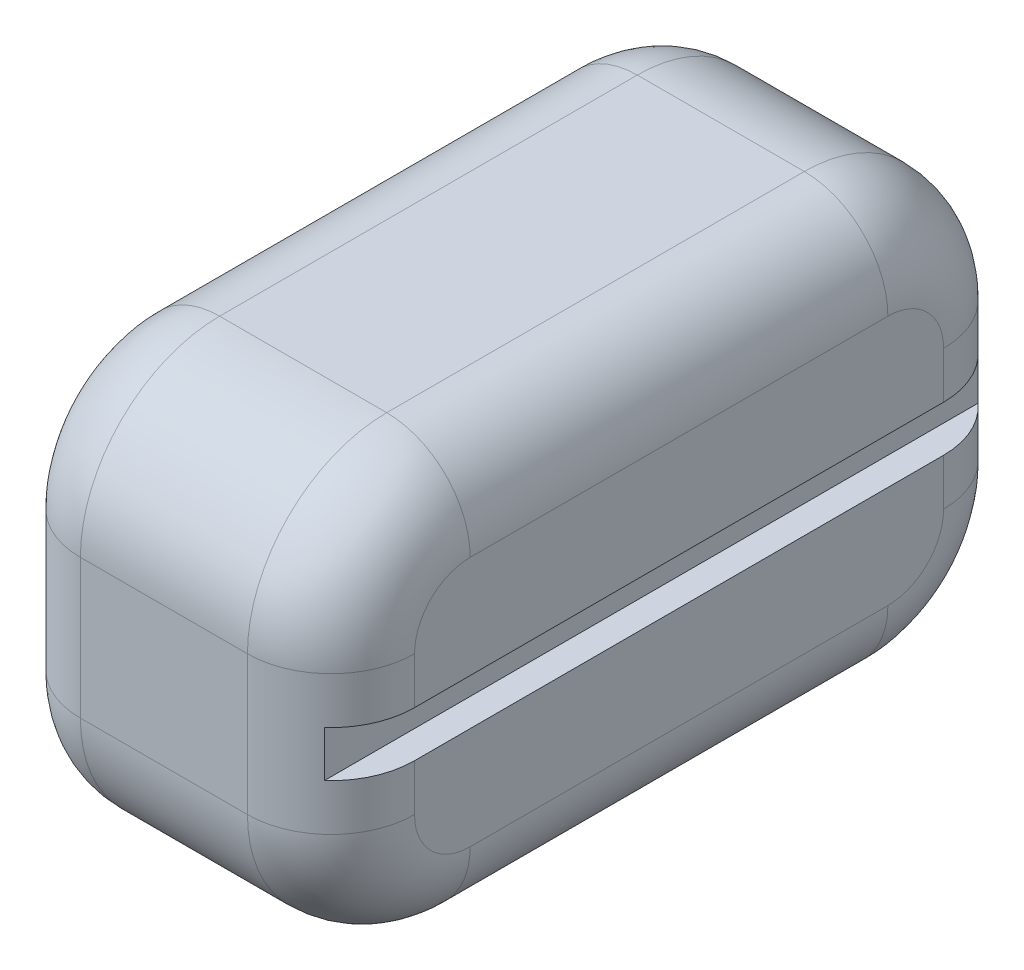
SolidWorks part; units mm, degrees
ref_plane "Front Plane" through (0, 0, 0) normal (0, 0, 1) x (1, 0, 0)
ref_plane "Top Plane" through (0, 0, 0) normal (0, 1, 0) x (1, 0, 0)
ref_plane "Right Plane" through (0, 0, 0) normal (1, 0, 0) x (0, 0, -1)
sketch "Sketch1" plane through (0, 0, 0) normal (1, 0, 0) x (0, 0, -1)
  line L1 (-12.5, -7.5) -> (12.5, -7.5)
  line L2 (-12.5, -7.5) -> (-12.5, 7.5)
  line L3 (-12.5, 7.5) -> (12.5, 7.5)
  line L4 (12.5, -7.5) -> (12.5, 7.5)
  line L5 (0, 7.5) -> (0, -7.5) construction
  line L6 (-12.5, 0) -> (12.5, 0) construction
  point P0 (0, 0)
  dimension "D1" = 15
  dimension "D2" = 25
extrude "Boss-Extrude1" add sketch "Sketch1" along normal blind 12
sketch "Sketch2" plane through (0, 0, 0) normal (0, 1, 0) x (1, 0, 0)
  line L8 (-4, 0) -> (10, 0) construction
  line L9 (0, -10.5) -> (10, -10.5)
  line L10 (10, -10.5) -> (10, 10.5)
  line L11 (10, 10.5) -> (0, 10.5)
  line L12 (-4, -10.5) -> (10, -10.5) construction
  line L13 (10, -10.5) -> (10, 10.5) construction
  line L14 (10, 10.5) -> (-4, 10.5) construction
  line L16 (-4, 12.5) -> (-4, -12.5)
  line L17 (-4, 12.5) -> (-4, -12.5) construction
  circle A3 centre (3, 0) radius 7
  dimension "D1" = 2
  dimension "D2" = 4
extrude "Cut-Extrude1" cut sketch "Sketch2" against normal mid plane 8
ref_plane "Plane1" through (0, -3.8, 0) normal (0, 1, 0) x (1, 0, 0)
sketch "Sketch3" plane through (0, -3.8, 0) normal (0, 1, 0) x (1, 0, 0)
  line L0 (0, -6.3246) -> (0, 6.3246) construction
  line L1 (0, -6.0467) -> (0, 6.0467)
  arc A2 (0.1071, -6.0987) -> (0.1071, 6.0987) centre (3, 0) ccw
  arc A3 (0, -6.0467) -> (0, 6.0467) centre (3, 0) ccw
  dimension "D1" = 0.25
extrude "Boss-Extrude2" add sketch "Sketch3" along normal blind 7.6 separate body
sketch "Sketch4" plane through (0, 0, 0) normal (-1, 0, 0) x (0, 0, 1)
  line L0 (6.0467, 3.8) -> (-6.0467, -3.8) construction
  line L1 (5.5, -3.8) -> (-5.5, -3.8) construction
  line L2 (-6.0467, 3.8) -> (-6.0467, -3.8) construction
  circle A0 centre (0, 0) radius 1.8
  dimension "D1" = 3.6
extrude "Cut-Extrude2" cut sketch "Sketch4" against normal blind 7
sketch "Sketch6" plane through (0, 0, 0) normal (-1, 0, 0) x (0, 0, 1)
  circle A0 centre (0, 0) radius 1.8 construction
  circle A1 centre (0, 0) radius 1.8
curve "Helix/Spiral1" pitch 5 height 5 radius 1.8 centre (0, 0, 0) axis (1, 0, 0) start towards (0, 1, 0)
sketch "Sketch7" plane through (0, 0, 0) normal (0, 0, 1) x (1, 0, 0)
  line L0 (0, 1.8) -> (-0.75, 1.8)
  line L1 (-0.75, 1.8) -> (0, 3.3)
  line L2 (0, 7.5) -> (0, -7.5) construction
  line L3 (0, 3.3) -> (0.75, 1.8)
  line L4 (0.75, 1.8) -> (0, 1.8)
  dimension "D1" = 0.75
  dimension "D2" = 1.5
sweep "Cut-Sweep1" cut profiles "Sketch7" path "Helix/Spiral1" align with end faces yes
chamfer "Chamfer1" distance 1 angle 45 1 edges at (0, -1.8, 0)
fillet "Fillet1" radius 5 4 edges at (6, -7.5, -12.5) (6, -7.5, 12.5) (6, 7.5, 12.5) (6, 7.5, -12.5)
fillet "Fillet2" radius 3 16 edges at (0, -6.0355, -11.0355) (0, -7.5, 0) (0, -6.0355, 11.0355) (0, 0, 12.5) (0, 6.0355, 11.0355) (0, 7.5, 0) (0, 6.0355, -11.0355) (12, -6.0355, 11.0355) (12, 0, 12.5) (12, 6.0355, 11.0355) (12, 7.5, 0) (12, 6.0355, -11.0355) (12, 0, -12.5) (12, -6.0355, -11.0355) (12, -7.5, 0) (0, 0, -12.5)
sketch "Sketch8" plane through (12, 0, 0) normal (1, 0, 0) x (0, 0, -1)
  line L0 (-12.5, -2.5) -> (-12.5, 2.5) construction
  line L1 (12.5, -0.825) -> (-12.5, -0.825)
  line L2 (12.5, -0.825) -> (12.5, 0.825)
  line L3 (12.5, 0.825) -> (-12.5, 0.825)
  line L4 (-12.5, -0.825) -> (-12.5, 0.825)
  line L5 (0, 0.825) -> (0, -0.825) construction
  line L6 (12.5, 0) -> (-12.5, 0) construction
  point P0 (0, 0)
  dimension "D1" = 1.65
extrude "Cut-Extrude3" cut sketch "Sketch8" against normal blind 1
